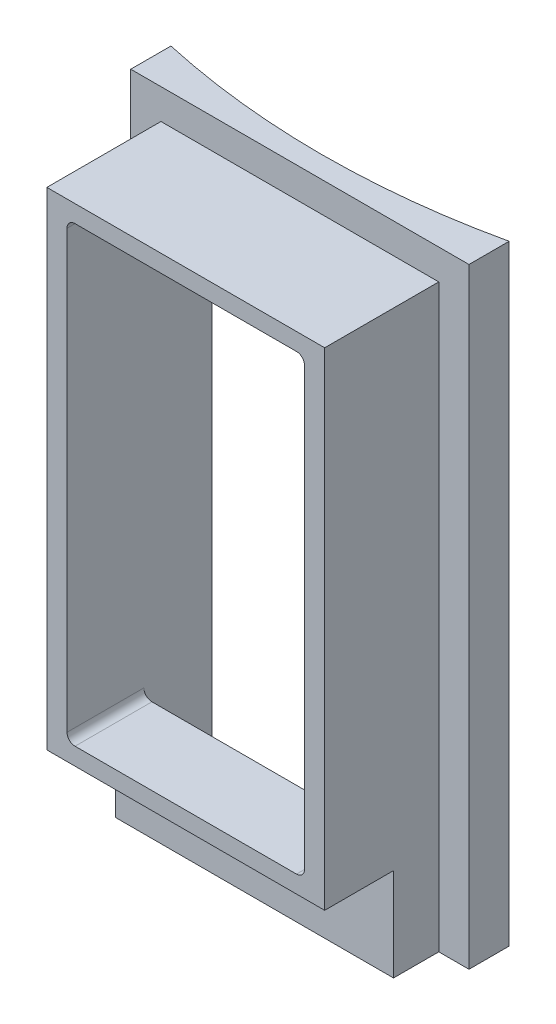
SolidWorks part; units mm, degrees
ref_plane "Front Plane" through (0, 0, 0) normal (0, 0, 1) x (1, 0, 0)
ref_plane "Top Plane" through (0, 0, 0) normal (0, 1, 0) x (1, 0, 0)
ref_plane "Right Plane" through (0, 0, 0) normal (1, 0, 0) x (0, 0, -1)
sketch "Sketch1" plane through (0, 0, 0) normal (0, 0, 1) x (1, 0, 0)
  line L1 (-46.99, 86.36) -> (59.69, 86.36)
  line L2 (-46.99, 86.36) -> (-46.99, -106.172)
  line L3 (-46.99, -106.172) -> (59.69, -106.172)
  line L4 (59.69, 86.36) -> (59.69, -106.172)
  dimension "D1" = 106.68
extrude "Extrude1" add sketch "Sketch1" along normal blind 252.4252
sketch "Sketch2" plane through (0, 86.36, 0) normal (0, 1, 0) x (-1, 0, 0)
  line L0 (-59.69, 0) -> (46.99, 0) construction
  circle A1 centre (-6.35, 0) radius 245.618
sketch "Sketch7" plane through (0, 0, 252.4252) normal (0, 0, 1) x (1, 0, 0)
  line L0 (-46.99, 86.36) -> (-46.99, -106.172) construction
  line L1 (-37.465, 76.835) -> (50.165, 76.835)
  line L2 (-37.465, 76.835) -> (-37.465, -106.172)
  line L3 (-37.465, -106.172) -> (50.165, -106.172)
  line L4 (50.165, 76.835) -> (50.165, -106.172)
  line L5 (59.69, -106.172) -> (59.69, 86.36) construction
  point P8 (6.35, 76.835)
  point P9 (0, 0)
  dimension "D1" = 9.525
  dimension "D2" = 9.525
extrude "Extrude5" add sketch "Sketch7" along normal blind 35.9842
sketch "Sketch4" plane through (0, 0, 252.4252) normal (0, 0, 1) x (1, 0, 0)
  line L0 (59.69, 86.36) -> (-46.99, 86.36) construction
  line L1 (-31.115, 71.374) -> (43.815, 71.374)
  line L2 (-31.115, 71.374) -> (-31.115, -71.374)
  line L3 (-31.115, -71.374) -> (43.815, -71.374)
  line L4 (43.815, 71.374) -> (43.815, -71.374)
  line L5 (50.165, 76.835) -> (-37.465, 76.835) construction
  point P4 (6.35, 71.374)
  point P5 (6.35, 86.36)
  point P6 (6.35, 76.835)
extrude "Extrude2" cut sketch "Sketch4" against normal blind 273.8502 and the other way blind 42.08
sketch "Sketch10" plane through (0, 0, 0) normal (0, 0, -1) x (-1, 0, 0)
  line L1 (-43.815, 71.374) -> (31.115, 71.374)
  line L2 (-43.815, 71.374) -> (-43.815, 74.295)
  line L3 (-43.815, 74.295) -> (31.115, 74.295)
  line L4 (31.115, 71.374) -> (31.115, 74.295)
  line L5 (-43.815, -71.374) -> (31.115, -71.374)
  line L6 (-43.815, -71.374) -> (-43.815, -103.632)
  line L7 (-43.815, -103.632) -> (31.115, -103.632)
  line L8 (31.115, -71.374) -> (31.115, -103.632)
extrude "Extrude8" cut sketch "Sketch10" against normal blind 264.16
sketch "Sketch11" plane through (0, 0, 264.16) normal (0, 0, -1) x (-1, 0, 0)
  line L0 (-43.815, 71.374) -> (31.115, 71.374) construction
  line L1 (31.115, 74.295) -> (-43.815, 74.295)
  line L2 (31.115, 74.295) -> (31.115, 71.374)
  line L3 (31.115, 71.374) -> (-43.815, 71.374)
  line L4 (-43.815, 74.295) -> (-43.815, 71.374)
extrude "Extrude9" cut sketch "Sketch11" against normal blind 21.59
fillet "Fillet1" radius 2.54 8 edges at (43.815, -71.374, 276.2847) (-31.115, -71.374, 276.2847) (43.815, 71.374, 287.0797) (-31.115, 71.374, 287.0797) (43.815, -103.632, 132.08) (-31.115, -103.632, 132.08) (-31.115, 74.295, 142.875) (43.815, 74.295, 142.875)
extrude "Extrude4" cut sketch "Sketch2" against normal blind 230
sketch "Sketch12" plane through (0, 0, 288.4094) normal (0, 0, 1) x (1, 0, 0)
  line L0 (50.165, -106.172) -> (50.165, 76.835) construction
  line L1 (-37.465, -106.172) -> (50.165, -106.172)
  line L2 (-37.465, -106.172) -> (-37.465, -76.835)
  line L3 (-37.465, -76.835) -> (50.165, -76.835)
  line L4 (50.165, -106.172) -> (50.165, -76.835)
extrude "Extrude10" cut sketch "Sketch12" against normal blind 21.7094
